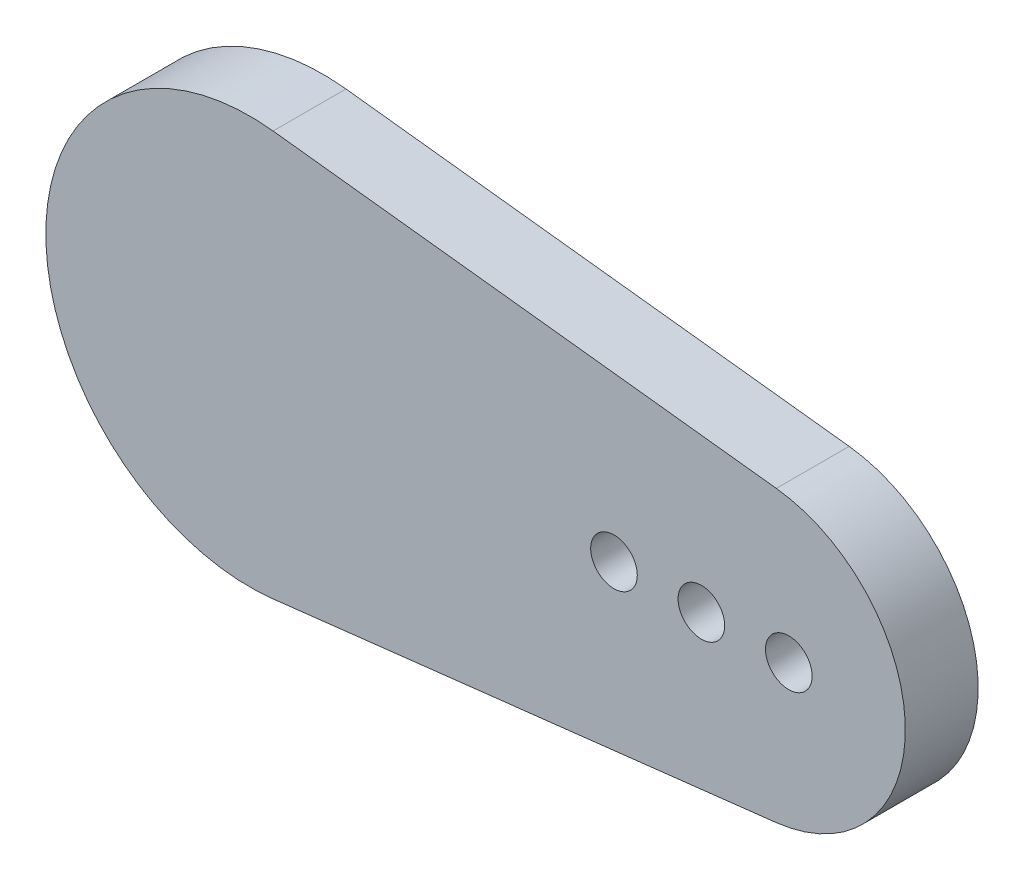
SolidWorks part; units mm, degrees
ref_plane "XY" through (0, 0, 0) normal (0, 0, 1) x (1, 0, 0)
ref_plane "XZ" through (0, 0, 0) normal (0, 1, 0) x (1, 0, 0)
ref_plane "YZ" through (0, 0, 0) normal (1, 0, 0) x (0, 0, -1)
ref_axis "X" through (-88.99, 0, 0) along (1, 0, 0)
ref_axis "Y" through (0, -55, 0) along (0, 1, 0)
ref_axis "Z" through (0, 0, 55) along (0, 0, -1)
sketch "Sketch1" plane through (0, 0, 0) normal (0, 0, 1) x (1, 0, 0)
  line L0 (0.8, -6.9541) -> (18.0714, -4.9672)
  line L1 (18.0714, 4.9672) -> (0.8, 6.9541)
  line L2 (0, 0) -> (17.5, 0) construction
  arc A2 (0.8, 6.9541) -> (0.8, -6.9541) centre (0, 0) ccw
  arc A3 (18.0714, -4.9672) -> (18.0714, 4.9672) centre (17.5, 0) ccw
  circle A4 centre (12.5, 0) radius 0.8
  circle A5 centre (15.5, 0) radius 0.8
  circle A6 centre (18.5, 0) radius 0.8
  dimension "D1" = 7
  dimension "D3" = 5
  dimension "D4" = 1.6
  dimension "D2" = 22.5
  dimension "D5" = 12.5
  dimension "D7" = 3
  dimension "D6" = 3
extrude "Boss-Extrude1" add sketch "Sketch1" along normal blind 2.5
